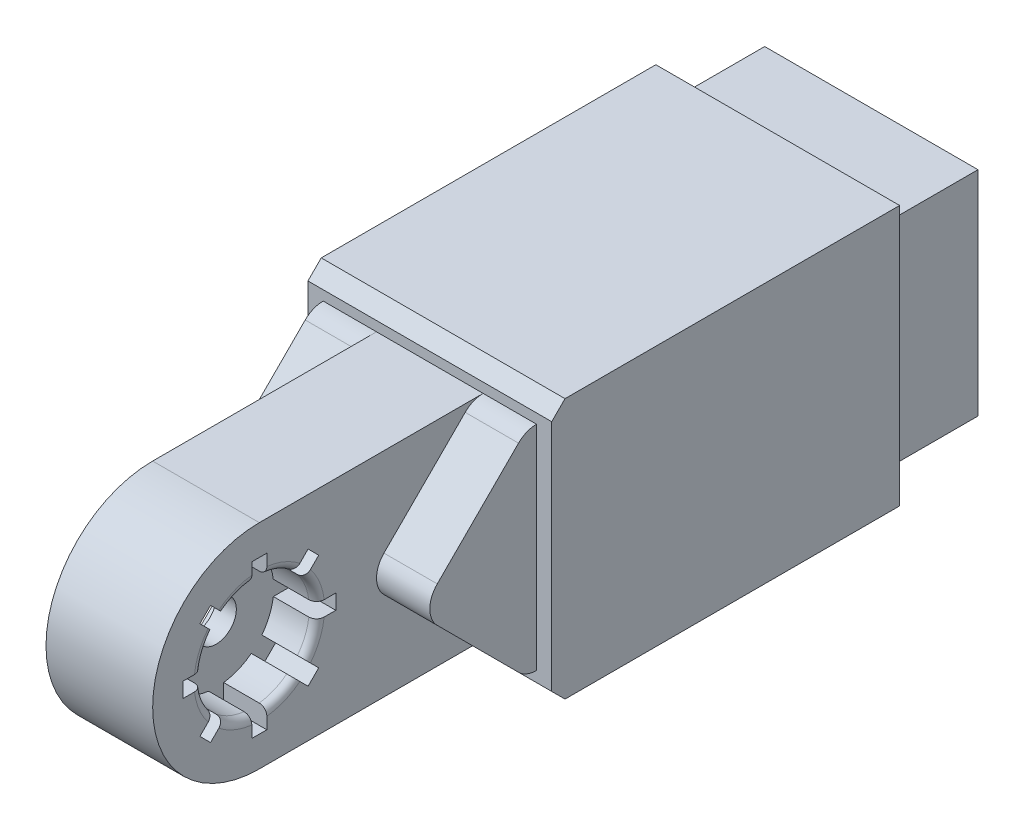
SolidWorks part; units mm, degrees
ref_plane "Front Plane" through (0, 0, 0) normal (0, 0, 1) x (1, 0, 0)
ref_plane "Top Plane" through (0, 0, 0) normal (0, 1, 0) x (1, 0, 0)
ref_plane "Right Plane" through (0, 0, 0) normal (1, 0, 0) x (0, 0, -1)
sketch "Sketch2" plane through (0, 0, 0) normal (0, 0, 1) x (1, 0, 0)
  line L1 (-21, 21) -> (21, 21)
  line L2 (-21, 21) -> (-21, -21)
  line L3 (-21, -21) -> (21, -21)
  line L4 (21, 21) -> (21, -21)
  line L5 (-21, 21) -> (21, -21) construction
  line L6 (-21, -21) -> (21, 21) construction
  point P0 (0, 0)
  dimension "D1" = 42
  dimension "D2" = 42
extrude "Boss-Extrude1" add sketch "Sketch2" along normal blind 89
ref_plane "Plane1" through (0, 0, 89) normal (0, 0, 1) x (1, 0, 0)
sketch "Sketch3" plane through (0, 0, 89) normal (0, 0, 1) x (1, 0, 0)
  line L0 (21, 21) -> (-21, 21) construction
  line L1 (10.5, -21) -> (-10.5, -21)
  line L2 (10.5, -21) -> (10.5, 21)
  line L3 (10.5, 21) -> (-10.5, 21)
  line L4 (-10.5, -21) -> (-10.5, 21)
  line L5 (10.5, -21) -> (-10.5, 21) construction
  line L6 (10.5, 21) -> (-10.5, -21) construction
  point P0 (0, 0)
  dimension "D1" = 21
ref_plane "Plane4" through (0, 0, 0) normal (0, 0, -1) x (-1, 0, 0)
extrude "Boss-Extrude2" add sketch "Sketch3" along normal blind 42
ref_plane "Plane5" through (-10.5, 0, 0) normal (-1, 0, 0) x (0, 0, 1)
sketch "Sketch8" plane through (-10.5, 0, 0) normal (-1, 0, 0) x (0, 0, 1)
  line L0 (131, 21) -> (131, -21) construction
  line L1 (131, 21) -> (131, -21)
  arc A0 (131, 21) -> (131, -21) centre (131, 0) cw
  dimension "D1" = 21
extrude "Boss-Extrude3" add sketch "Sketch8" against normal blind 21
ref_plane "Plane6" through (-10.5, 0, 0) normal (-1, 0, 0) x (0, 0, 1)
sketch "Sketch9" plane through (-10.5, 0, 0) normal (-1, 0, 0) x (0, 0, 1)
  line L0 (89, 21) -> (89, -21) construction
  line L1 (131, 21) -> (131, -21)
  circle A0 centre (131, 0) radius 11.35
  dimension "D1" = 42
  dimension "D2" = 22.7
extrude "Cut-Extrude2" cut sketch "Sketch9" against normal blind 8.5 contours A0
ref_plane "Plane7" through (10.5, 0, 0) normal (1, 0, 0) x (0, 0, -1)
sketch "Sketch11" plane through (10.5, 0, 0) normal (1, 0, 0) x (0, 0, -1)
  line L0 (-131, 21) -> (-131, -21)
  circle A0 centre (-131, 0) radius 11.35
  dimension "D1" = 22.7
extrude "Cut-Extrude3" cut sketch "Sketch11" against normal blind 8.5 contours A0
ref_plane "Plane8" through (-2, 0, 0) normal (-1, 0, 0) x (0, 0, 1)
sketch "Sketch12" plane through (-2, 0, 0) normal (-1, 0, 0) x (0, 0, 1)
  circle A0 centre (131, 0) radius 3.975
  dimension "D1" = 7.95
extrude "Cut-Extrude4" cut sketch "Sketch12" against normal through all
ref_plane "Plane10" through (-2, 0, 0) normal (-1, 0, 0) x (0, 0, 1)
ref_plane "Plane11" through (-10.5, 0, 0) normal (-1, 0, 0) x (0, 0, 1)
sketch "Sketch20" plane through (-10.5, 0, 0) normal (-1, 0, 0) x (0, 0, 1)
  line L0 (131, 0) -> (110, 0)
  line L1 (110, 0) -> (110, 21)
  line L2 (110, 0) -> (110, -21)
  line L4 (110, 21) -> (89, 21)
  line L6 (110, -21) -> (89, -21)
  line L7 (89, 21) -> (110, 0)
  line L8 (89, -21) -> (110, 0)
  line L9 (89, 21) -> (89, -21)
  circle A0 centre (131, 0) radius 11.35
  dimension "D1" = 21
extrude "Boss-Extrude4" add sketch "Sketch20" along normal blind 10.5 and the other way blind 31.5 contours L7 L9 L8 region at (-10.5, 0, 96)
fillet "Fillet1" radius 5 1 edges at (15.75, 0, 110)
fillet "Fillet2" radius 5 1 edges at (-15.75, 0, 110)
fillet "Fillet3" radius 5 1 edges at (-15.75, -21, 89)
fillet "Fillet4" radius 5 1 edges at (-15.75, 21, 89)
fillet "Fillet5" radius 5 1 edges at (15.75, -21, 89)
fillet "Fillet6" radius 5 1 edges at (15.75, 21, 89)
fillet "Fillet7" radius 1.5 1 edges at (-10.5, 0, 142.35)
fillet "Fillet8" radius 1.5 1 edges at (10.5, 0, 119.65)
sketch "Sketch21" plane through (-10.5, 0, 0) normal (-1, 0, 0) x (0, 0, 1)
  line L1 (129.5207, 10.6415) -> (132.4793, 10.6415)
  line L2 (129.5207, 10.6415) -> (129.5207, 15.0585)
  line L3 (129.5207, 15.0585) -> (132.4793, 15.0585)
  line L4 (132.4793, 10.6415) -> (132.4793, 15.0585)
  line L5 (129.5207, 10.6415) -> (132.4793, 15.0585) construction
  line L6 (129.5207, 15.0585) -> (132.4793, 10.6415) construction
  circle A0 centre (131, 0) radius 12.85 construction
  point P0 (131, 12.85)
  dimension "D1" = 4.417
extrude "Cut-Extrude5" cut sketch "Sketch21" against normal blind 8.5
pattern_circular "CirPattern2" count 8 over 360 about axis through (-9, 0, 131) along (-1, 0, 0) of "Cut-Extrude5"
ref_plane "Plane12" through (0, 21, 0) normal (0, 1, 0) x (1, 0, 0)
ref_plane "Plane13" through (10.5, 0, 0) normal (1, 0, 0) x (0, 0, -1)
ref_plane "Plane14" through (0, 0, 0) normal (1, 0, 0) x (0, 0, -1)
mirror "Mirror1" about plane through (0, 0, 0) normal (1, 0, 0) of "CirPattern2"
ref_plane "Plane15" through (21, 0, 0) normal (1, 0, 0) x (0, 0, -1)
sketch "Sketch24" plane through (21, 0, 0) normal (1, 0, 0) x (0, 0, -1)
  line L1 (-86.9289, 21) -> (0, 21)
  line L2 (-86.9289, 21) -> (-86.9289, 25.5452)
  line L3 (-86.9289, 25.5452) -> (0, 25.5452)
  line L4 (0, 21) -> (0, 25.5452)
  line L5 (-86.9289, -21) -> (0, -21)
  line L6 (-86.9289, -21) -> (-86.9289, -25.6891)
  line L7 (-86.9289, -25.6891) -> (0, -25.6891)
  line L8 (0, -21) -> (0, -25.6891)
extrude "Boss-Extrude6" add sketch "Sketch24" against normal blind 42
sketch "Sketch25" plane through (21, 0, 0) normal (1, 0, 0) x (0, 0, -1)
  line L0 (-18.4289, -25.6891) -> (-18.4289, 25.5452)
  line L1 (-86.9289, 25.5452) -> (-18.4289, 25.5452)
  line L2 (-86.9289, 25.5452) -> (-86.9289, -25.6891)
  line L3 (-86.9289, -25.6891) -> (-18.4289, -25.6891)
  dimension "D1" = 68.5
extrude "Boss-Extrude7" add sketch "Sketch25" along normal blind 3
ref_plane "Plane18" through (0, 0, 0) normal (0, 0, -1) x (-1, 0, 0)
ref_plane "Plane19" through (-21, 0, 0) normal (-1, 0, 0) x (0, 0, 1)
sketch "Sketch28" plane through (-21, 0, 0) normal (-1, 0, 0) x (0, 0, 1)
  line L0 (86.9289, -25.6891) -> (0, -25.6891) construction
  line L1 (86.9289, 25.5452) -> (18.4289, 25.5452)
  line L2 (86.9289, 25.5452) -> (86.9289, -25.6891)
  line L3 (86.9289, -25.6891) -> (18.4289, -25.6891)
  line L4 (18.4289, 25.5452) -> (18.4289, -25.6891)
  dimension "D1" = 68.5
extrude "Boss-Extrude8" add sketch "Sketch28" along normal blind 3
ref_plane "Plane20" through (-24, 0, 0) normal (-1, 0, 0) x (0, 0, 1)
sketch "Sketch30" plane through (-24, 0, 0) normal (-1, 0, 0) x (0, 0, 1)
  line L1 (81.9289, 20.4302) -> (19.9289, 20.4302)
  line L2 (81.9289, 20.4302) -> (81.9289, -20.5741)
  line L3 (81.9289, -20.5741) -> (19.9289, -20.5741)
  line L4 (19.9289, 20.4302) -> (19.9289, -20.5741)
  line L5 (81.9289, 20.4302) -> (19.9289, -20.5741) construction
  line L6 (81.9289, -20.5741) -> (19.9289, 20.4302) construction
  line L8 (86.9289, 25.5452) -> (18.4289, 25.5452) construction
  line L9 (18.4289, -25.6891) -> (86.9289, -25.6891) construction
  line L10 (86.9289, -21) -> (86.9289, 21) construction
  point P0 (50.9289, -0.0719)
  dimension "D1" = 5.115
  dimension "D2" = 5.115
  dimension "D3" = 62
  dimension "D4" = 5
extrude "Cut-Extrude6" cut sketch "Sketch30" against normal blind 45
ref_plane "Plane21" through (21, 0, 0) normal (1, 0, 0) x (0, 0, -1)
sketch "Sketch31" plane through (21, 0, 0) normal (1, 0, 0) x (0, 0, -1)
  line L0 (0, -25.6891) -> (0, 25.5452) construction
  line L1 (-18.4289, -25.6891) -> (0, -25.6891)
  line L2 (-18.4289, -25.6891) -> (-18.4289, -21.0741)
  line L3 (-18.4289, -21.0741) -> (0, -21.0741)
  line L4 (0, -25.6891) -> (0, -21.0741)
  line L6 (-18.4289, 25.5452) -> (0, 25.5452)
  line L7 (-18.4289, 25.5452) -> (-18.4289, 20.9302)
  line L8 (-18.4289, 20.9302) -> (0, 20.9302)
  line L9 (0, 25.5452) -> (0, 20.9302)
  dimension "D1" = 4.615
  dimension "D2" = 4.615
extrude "Cut-Extrude7" cut sketch "Sketch31" against normal through all
chamfer "Chamfer1" distance 1.5 angle 45 4 edges at (0, 20.9302, 18.4289) (21, -0.0719, 18.4289) (0, -21.0741, 18.4289) (-21, -0.0719, 18.4289)
ref_plane "Plane22" through (0, 0, 0) normal (0, 0, -1) x (-1, 0, 0)
sketch "Sketch32" plane through (0, 0, 0) normal (0, 0, -1) x (-1, 0, 0)
  line L1 (15, 15) -> (-15, 15)
  line L2 (15, 15) -> (15, -15)
  line L3 (15, -15) -> (-15, -15)
  line L4 (-15, 15) -> (-15, -15)
  line L5 (15, 15) -> (-15, -15) construction
  line L6 (15, -15) -> (-15, 15) construction
  point P0 (0, 0)
  dimension "D1" = 30
  dimension "D2" = 30
extrude "Cut-Extrude8" cut sketch "Sketch32" against normal blind 16.8
ref_plane "Plane23" through (0, 0, 19.9289) normal (0, 0, 1) x (1, 0, 0)
sketch "Sketch33" plane through (0, 0, 19.9289) normal (0, 0, 1) x (1, 0, 0)
  circle A0 centre (0, 0) radius 5
  dimension "D1" = 10
extrude "Cut-Extrude9" cut sketch "Sketch33" against normal blind 16.8
ref_plane "Plane24" through (-21, 0, 0) normal (-1, 0, 0) x (0, 0, 1)
sketch "Sketch34" plane through (-24, 0, 0) normal (-1, 0, 0) x (0, 0, 1)
  line L0 (86.9289, -0.0719) -> (103.6427, -0.0719) construction
  line L2 (88.3304, -21.6696) -> (88.3304, -28.2221)
  line L3 (88.3304, -28.2221) -> (81.7779, -28.2221)
  line L4 (81.7779, -28.2221) -> (88.3304, -21.6696)
  line L5 (86.9289, -25.6891) -> (86.9289, 25.5452) construction
  line L6 (88.3304, 28.0782) -> (81.7779, 28.0782)
  line L7 (88.3304, 21.5257) -> (88.3304, 28.0782)
  line L8 (81.7779, 28.0782) -> (88.3304, 21.5257)
extrude "Cut-Extrude10" cut sketch "Sketch34" against normal through all
